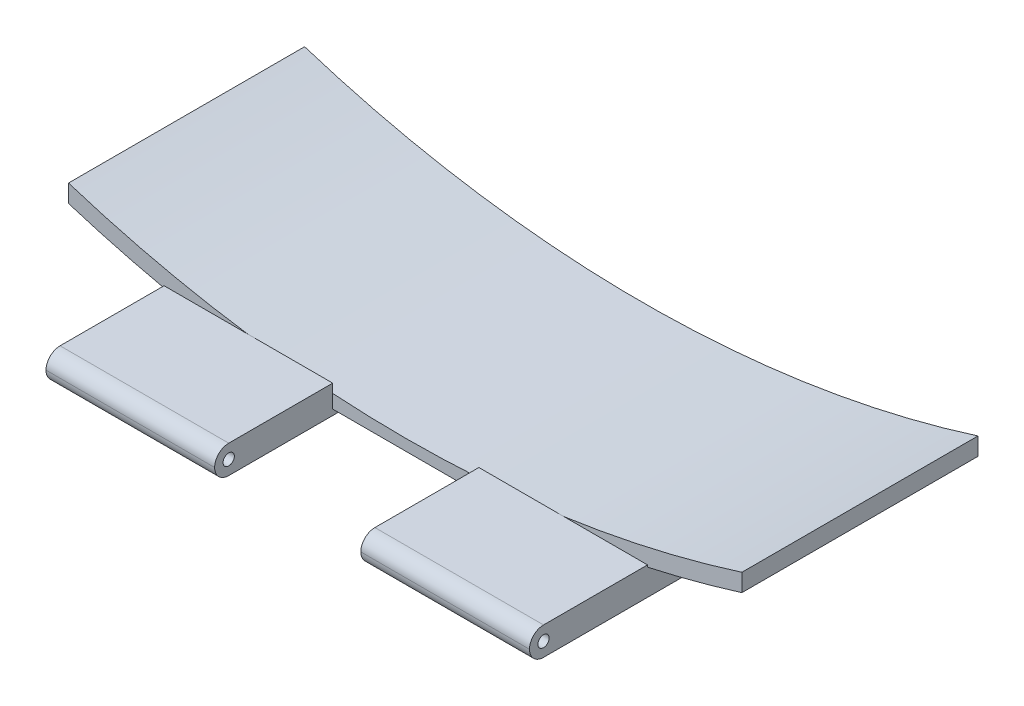
SolidWorks part; units mm, degrees
ref_plane "Plano frontal" through (0, 0, 0) normal (0, 0, 1) x (1, 0, 0)
ref_plane "Plano superior" through (0, 0, 0) normal (0, 1, 0) x (1, 0, 0)
ref_plane "Plano direito" through (0, 0, 0) normal (1, 0, 0) x (0, 0, -1)
sketch "Esboço1" plane through (0, 0, 0) normal (0, 0, 1) x (1, 0, 0)
  line L0 (-69.056, 72.3275) -> (-69.0975, 72.3275)
  line L4 (-69.0975, 72.3275) -> (-69.0975, 72.2879)
  line L7 (59.8257, 72.2579) -> (59.8257, 69.1129)
  line L9 (-59.9557, 72.3275) -> (-59.9557, 69.1813)
  line L11 (-42.9557, 64.6567) -> (-42.9557, 60.0035)
  line L12 (-42.9557, 60.0035) -> (43.0443, 60.0035)
  line L13 (43.0443, 64.6567) -> (43.0443, 60.0035)
  arc A0 (43.0443, 64.6567) -> (-42.9557, 64.6567) centre (0.0443, 260.4138) ccw
  circle A1 centre (0.0443, 260.4138) radius 197.4246
  arc A2 (69.1179, 72.2684) -> (-69.0975, 72.2879) centre (0, 0) ccw
  point P5 (0.0443, 59.9896)
  point P6 (-69.0975, 72.2879)
  dimension "D1" = 86
  dimension "D2" = 200
extrude "Ressalto-extrusão1" add sketch "Esboço1" along normal blind 42 contours A1 L9 L7 region at (-0.0711, 61.7851, 0)
ref_plane "Plane1" through (-59.9557, 69.1813, 42) normal (0.9541, -0.2994, 0) x (0, 0, -1)
sketch "Sketch5" plane through (0, 0, 42) normal (0, 0, 1) x (1, 0, 0)
  line L1 (-42.9557, 60.0035) -> (-12.9557, 60.0035)
  line L2 (-42.9557, 60.0035) -> (-42.9557, 65.0035)
  line L3 (-42.9557, 65.0035) -> (-12.9557, 65.0035)
  line L4 (-12.9557, 60.0035) -> (-12.9557, 65.0035)
  line L5 (43.0443, 60.0035) -> (13.0443, 60.0035)
  line L6 (-7.815, 77.3824) -> (-7.815, 47.3628) construction
  line L7 (43.0443, 60.0035) -> (43.0443, 65.0035)
  line L8 (43.0443, 65.0035) -> (13.0443, 65.0035)
  line L9 (13.0443, 60.0035) -> (13.0443, 65.0035)
  dimension "D1" = 30
  dimension "D2" = 30
extrude "Boss-Extrude3" add sketch "Sketch5" along normal blind 21
fillet "Fillet1" radius 2.5 4 edges at (-27.9557, 65.0035, 63) (-27.9557, 60.0035, 63) (28.0443, 65.0035, 63) (28.0443, 60.0035, 63)
chamfer "Chamfer1" distance 1 angle 45 1 edges
sketch "Esboço2" plane through (-42.9557, 0, 0) normal (-1, 0, 0) x (0, 0, 1)
  line L0 (63, 62.5035) -> (60.5, 62.5035) construction
  circle A0 centre (60.5, 62.5035) radius 1
  dimension "D2" = 2
  dimension "D1" = 2.5
extrude "Corte-extrusão1" cut sketch "Esboço2" against normal through all
